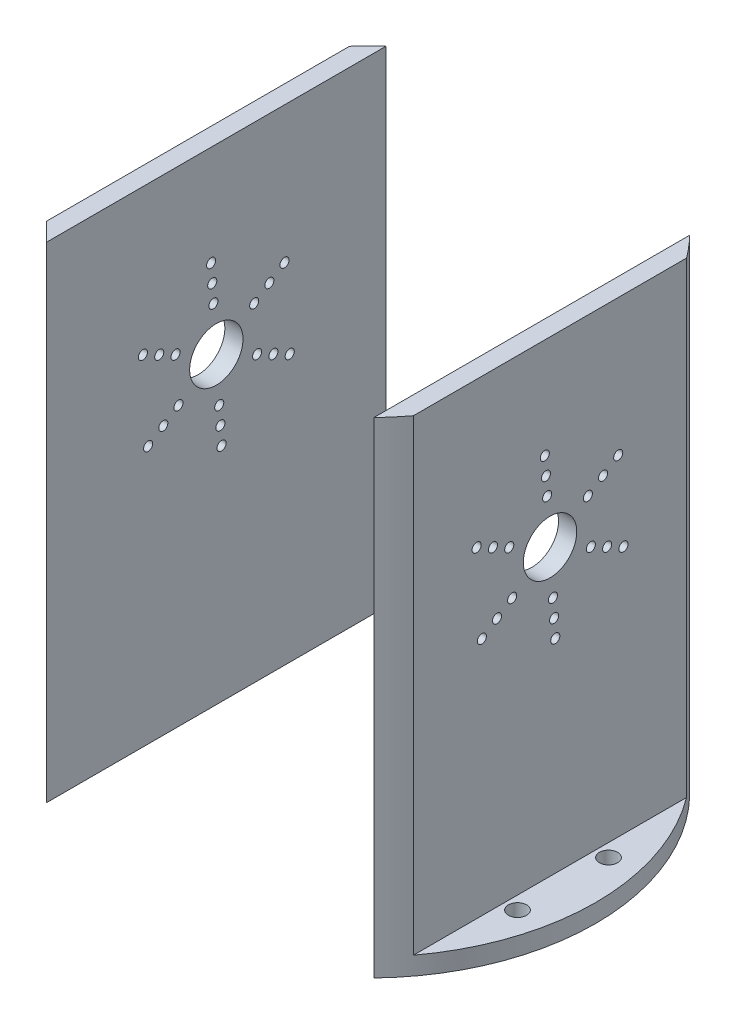
SolidWorks part; units mm, degrees
material "Aluminium 1050"
ref_plane "Front Plane" through (0, 0, 0) normal (0, 0, 1) x (1, 0, 0)
ref_plane "Top Plane" through (0, 0, 0) normal (0, 1, 0) x (1, 0, 0)
ref_plane "Right Plane" through (0, 0, 0) normal (1, 0, 0) x (0, 0, -1)
sketch "Sketch1" plane through (0, 0, 0) normal (0, 1, 0) x (1, 0, 0)
  line L0 (-25, 0) -> (-25, 27.9508)
  line L1 (0, 37.5) -> (0, -37.5) construction
  line L2 (-25, 0) -> (-25, -27.9508)
  line L3 (-28, 0) -> (-28, -24.9449)
  line L4 (-28, 0) -> (-28, 24.9449)
  line L5 (-28, 0) -> (-28, 27.9508) construction
  line L6 (-28, 0) -> (-28, -27.9508) construction
  line L7 (25, -27.9508) -> (25, 27.9508)
  line L8 (-37.5, 0) -> (37.5, 0) construction
  line L9 (27, -26.024) -> (27, 26.024)
  line L10 (30, -22.5) -> (30, 22.5)
  line L11 (30, -27.9508) -> (30, 27.9508) construction
  line L12 (27, -27.9508) -> (27, 27.9508) construction
  circle A0 centre (0, 0) radius 37.5
  circle A1 centre (0, 0) radius 25
  point P19 (25, 0)
  dimension "D1" = 75
  dimension "D2" = 50
  dimension "D3" = 3
  dimension "D4" = 2
  dimension "D5" = 3
extrude "Boss-Extrude1" add sketch "Sketch1" along normal blind 3 contours L4 A0 L3 | L0 A0 L4 L3 L2 | L10 A0 | L9 A0 L10 region at (-26.4717, 0, 0) region at (-31.8445, 0, 0) region at (28.4639, 0, 0) region at (33.0273, 0, 0)
extrude "Boss-Extrude2" add sketch "Sketch1<3>" along normal blind 80 contours L0 A0 L4 L3 L2 | L9 A0 L10 region at (-26.4717, 0, 0) region at (28.4639, 0, 0)
sketch "Sketch1<3>" plane through (0, 0, 0) normal (0, 1, 0) x (1, 0, 0) same geometry as "Sketch1"
sketch "Sketch4" plane through (27, 0, 0) normal (-1, 0, 0) x (0, 0, 1)
  line L0 (0, 80) -> (0, 3)
  line L1 (24.9449, 80) -> (-24.9449, 80) construction
  line L2 (24.9449, 3) -> (-24.9449, 3) construction
  line L3 (-24.9449, 41.5) -> (24.9449, 41.5)
  line L4 (-24.9449, 80) -> (-24.9449, 3) construction
  line L5 (24.9449, 80) -> (24.9449, 3) construction
sketch "Sketch7" plane through (27, 0, 0) normal (-1, 0, 0) x (0, 0, 1)
  line L0 (-24.9449, 80) -> (24.9449, 80)
  line L2 (-24.9449, 50) -> (24.9449, 50) construction
  circle A19 centre (0.8632, 63.4724) radius 0.75
  circle A20 centre (0.6713, 60.4785) radius 0.75
  circle A21 centre (0.4795, 57.4847) radius 0.75
  circle A22 centre (12.099, 55.9887) radius 0.75
  circle A23 centre (9.4103, 54.6579) radius 0.75
  circle A24 centre (6.7217, 53.327) radius 0.75
  circle A25 centre (6.2421, 45.8424) radius 0.75
  circle A26 centre (8.739, 44.1793) radius 0.75
  circle A27 centre (11.2358, 42.5163) radius 0.75
  circle A28 centre (-0.8632, 36.5276) radius 0.7523
  circle A29 centre (-0.6713, 39.5215) radius 0.75
  circle A30 centre (-0.4795, 42.5153) radius 0.75
  circle A31 centre (-11.2358, 57.4837) radius 0.75
  circle A32 centre (-8.739, 55.8207) radius 0.75
  circle A33 centre (-6.2421, 54.1576) radius 0.75
  circle A34 centre (-12.099, 44.0113) radius 0.75
  circle A35 centre (-9.4103, 45.3421) radius 0.75
  circle A36 centre (-6.7217, 46.673) radius 0.75
  circle A37 centre (0, 50) radius 4.4
  dimension "D1" = 30
sketch "Sketch8" plane through (0, 3, 0) normal (0, 1, 0) x (1, 0, 0)
  line L0 (-37.5, 0) -> (37.5, 0) construction
  line L1 (-37.5, -7.5) -> (37.5, -7.5) construction
  line L2 (-37.5, 7.5) -> (37.5, 7.5) construction
  arc A0 (-28, 24.9449) -> (-28, -24.9449) centre (0, 0) ccw construction
  arc A1 (30, -22.5) -> (30, 22.5) centre (0, 0) ccw construction
  circle A2 centre (0, 0) radius 33 construction
  circle A4 centre (-32.1364, -7.5) radius 1.5
  circle A5 centre (32.1364, -7.5) radius 1.5
  circle A6 centre (32.1364, 7.5) radius 1.5
  circle A7 centre (-32.1364, 7.5) radius 1.5
  dimension "D3" = 66
  dimension "D4" = 3
  dimension "D5" = 3
  dimension "D6" = 3
  dimension "D7" = 3
  dimension "D1" = 7.5
  dimension "D2" = 7.5
extrude "Cut-Extrude2" cut sketch "Sketch8" against normal up to surface (3 mm away) up to face at (-25, 0, -13.9754)
extrude "Cut-Extrude3" cut sketch "Sketch7" against normal through all both and the other way through all contours A20 | A37 L2 | A21 | L2 A37 | A24 | A23 | A22 | A19 | A32 | A33 | A31 | A34 | A35 | A36 | A30 | A29 | A28 | A27 | A26 | A25 region at (27, 51.8674, 0) region at (27, 48.1326, 0) region at (27, 63.4724, 0.8632) region at (27, 60.4785, 0.6713) region at (27, 57.4847, 0.4795) region at (27, 55.9887, 12.099) region at (27, 54.6579, 9.4103) region at (27, 53.327, 6.7217) region at (27, 45.8424, 6.2421) region at (27, 44.1793, 8.739) region at (27, 42.5163, 11.2358) region at (27, 36.5276, -0.8632) region at (27, 39.5215, -0.6713) region at (27, 42.5153, -0.4795) region at (27, 57.4837, -11.2358) region at (27, 55.8207, -8.739) region at (27, 54.1576, -6.2421) region at (27, 44.0113, -12.099) region at (27, 45.3421, -9.4103) region at (27, 46.673, -6.7217)
